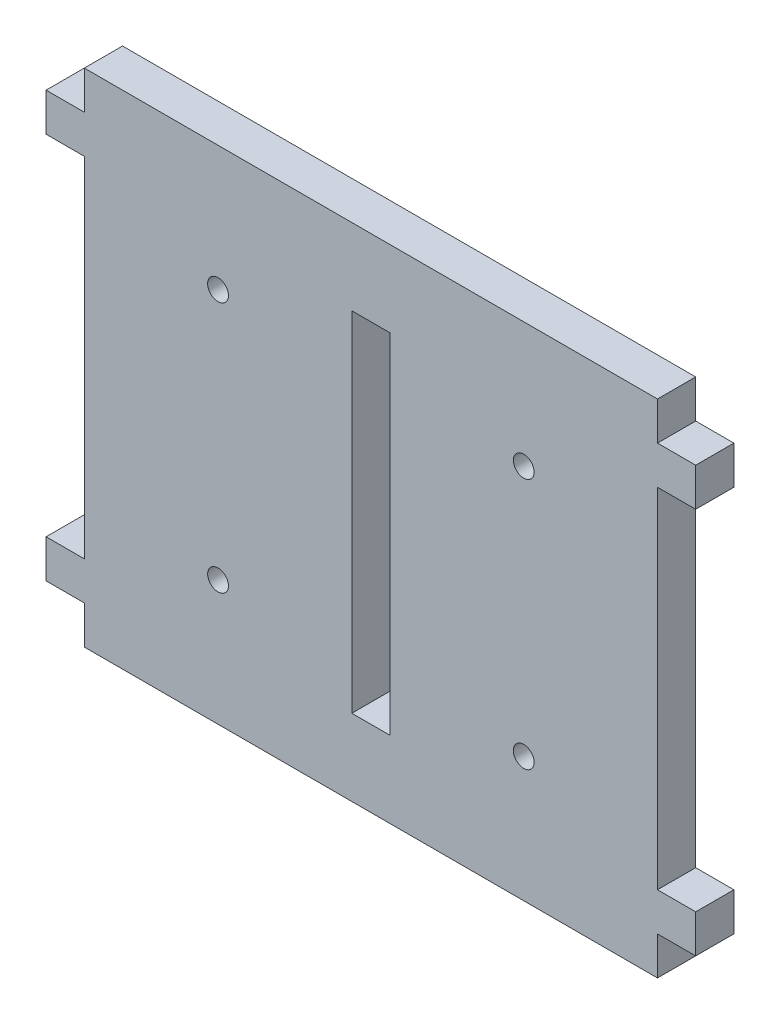
SolidWorks part; units mm, degrees
material "Acrylic (Medium-high impact)"
ref_plane "Front Plane" through (0, 0, 0) normal (0, 0, 1) x (1, 0, 0)
ref_plane "Top Plane" through (0, 0, 0) normal (0, 1, 0) x (1, 0, 0)
ref_plane "Right Plane" through (0, 0, 0) normal (1, 0, 0) x (0, 0, -1)
sketch "Sketch1" plane through (0, 0, 0) normal (0, 0, 1) x (1, 0, 0)
  line L0 (-101.6, 35.3139) -> (-107.95, 35.3139)
  line L1 (0, 35.3139) -> (-6.35, 35.3139)
  line L2 (0, 35.3139) -> (0, 28.9639)
  line L3 (0, -35.3139) -> (-6.35, -35.3139)
  line L4 (-107.95, 35.3139) -> (-107.95, 28.9639)
  line L5 (-101.6, -35.3139) -> (-107.95, -35.3139)
  line L6 (-6.35, 35.3139) -> (-6.35, 41.6639)
  line L7 (-6.35, 41.6639) -> (-101.6, 41.6639)
  line L8 (-101.6, 35.3139) -> (-101.6, 41.6639)
  line L9 (0, -28.9639) -> (0, -35.3139)
  line L10 (-6.35, -35.3139) -> (-6.35, -41.6639)
  line L11 (-6.35, -41.6639) -> (-101.6, -41.6639)
  line L12 (-101.6, -35.3139) -> (-101.6, -41.6639)
  line L13 (-107.95, -28.9639) -> (-107.95, -35.3139)
  line L16 (-50.8, -28.9639) -> (-50.8, 28.9639)
  line L17 (-57.15, -28.9639) -> (-50.8, -28.9639)
  line L18 (-57.15, 28.9639) -> (-57.15, -28.9639)
  line L19 (-50.8, 28.9639) -> (-57.15, 28.9639)
  line L20 (-50.8, -28.9639) -> (-50.8, 28.9639)
  line L21 (-57.15, -28.9639) -> (-50.8, -28.9639)
  line L22 (-57.15, 28.9639) -> (-57.15, -28.9639)
  line L23 (-50.8, 28.9639) -> (-57.15, 28.9639)
  line L24 (0, -28.9639) -> (0, 28.9639)
  line L25 (-6.35, -28.9639) -> (0, -28.9639)
  line L26 (-6.35, 28.9639) -> (-6.35, -28.9639)
  line L27 (0, 28.9639) -> (-6.35, 28.9639)
  line L29 (-6.35, -28.9639) -> (0, -28.9639)
  line L30 (-6.35, 28.9639) -> (-6.35, -28.9639)
  line L31 (0, 28.9639) -> (-6.35, 28.9639)
  line L32 (-101.6, -28.9639) -> (-101.6, 28.9639)
  line L33 (-107.95, -28.9639) -> (-101.6, -28.9639)
  line L34 (-107.95, 28.9639) -> (-107.95, -28.9639)
  line L35 (-101.6, 28.9639) -> (-107.95, 28.9639)
  line L36 (-101.6, -28.9639) -> (-101.6, 28.9639)
  line L37 (-107.95, -28.9639) -> (-101.6, -28.9639)
  line L39 (-101.6, 28.9639) -> (-107.95, 28.9639)
  dimension "D1" = 0
  dimension "D2" = 0
  dimension "D3" = 0
extrude "Boss-Extrude1" add sketch "Sketch1" along normal blind 6.35
hole_wizard "Tap Drill for #8-32 Tap2" positions "Sketch4" profile "Sketch5" hole size "#8-32" standard "ANSI Inch" end condition through all
sketch "Sketch4" plane through (81.8709, 75.287, -78.0748) normal (0, 0, -1) x (0, -1, 0)
  point P0 (54.4003, 110.4459)
  point P3 (96.1738, 110.4459)
  point P6 (96.1738, 161.2459)
  point P11 (54.4003, 161.2459)
sketch "Sketch5" plane through (-28.575, 20.8867, -78.0748) normal (1, 0, 0) x (0, 1, 0)
  line L0 (0, 0) -> (0, 84.4248)
  line L1 (0, 84.4248) -> (1.7272, 84.4248)
  line L2 (1.7272, 84.4248) -> (1.7272, 0)
  line L3 (1.7272, 0) -> (0, 0)
  line L4 (0, -6.35) -> (0, 107.95) construction
  dimension "Thru Hole Dia." = 3.4544
  dimension "Thru Hole Depth" = 84.4248
